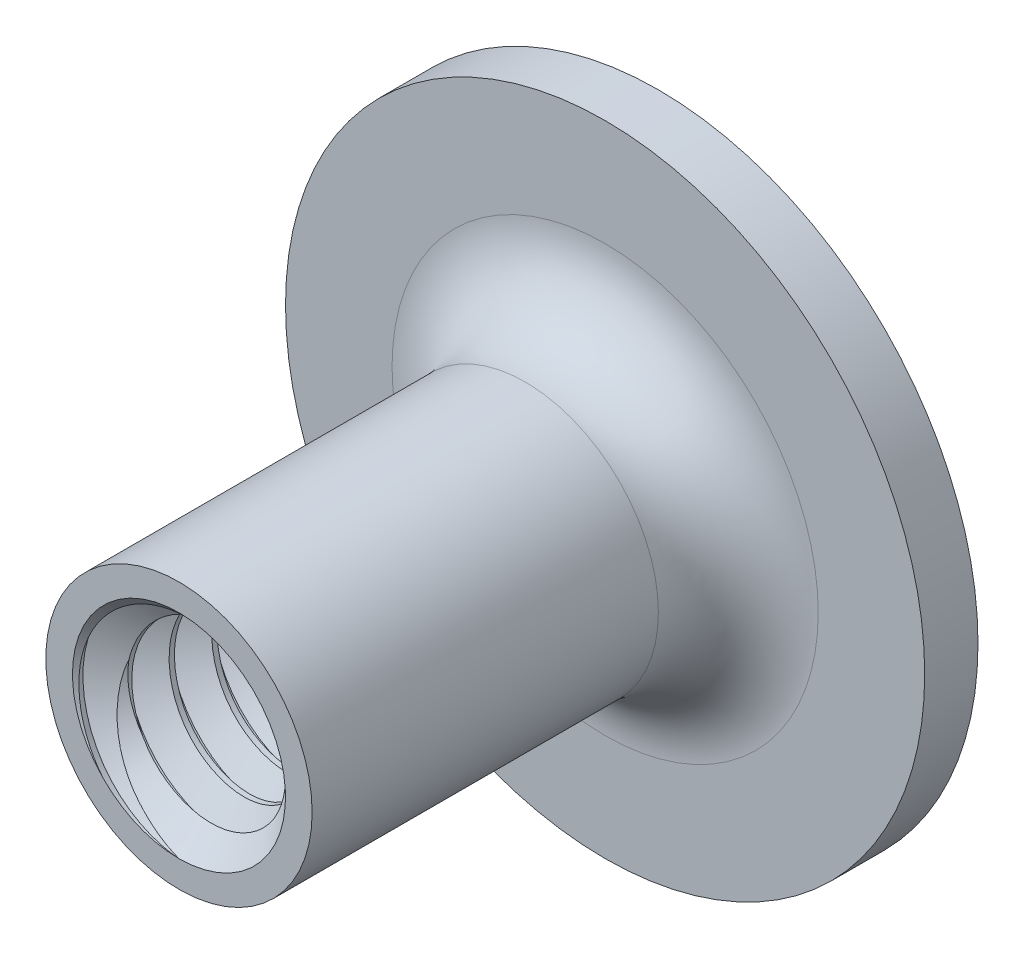
SolidWorks part; units mm, degrees
ref_plane "Front Plane" through (0, 0, 0) normal (0, 0, 1) x (1, 0, 0)
ref_plane "Top Plane" through (0, 0, 0) normal (0, 1, 0) x (1, 0, 0)
ref_plane "Right Plane" through (0, 0, 0) normal (1, 0, 0) x (0, 0, -1)
sketch "Sketch1" plane through (0, 0, 0) normal (0, 0, 1) x (1, 0, 0)
  circle A0 centre (0, 0) radius 9.525
  circle A1 centre (0, 0) radius 3.175
  dimension "D1" = 6.35
  dimension "base dia" = 19.05
extrude "Extrude1" add sketch "Sketch1" along normal blind 1.5875
sketch "Sketch2" plane through (0, 0, 1.5875) normal (0, 0, 1) x (1, 0, 0)
  circle A0 centre (0, 0) radius 3.9688
  circle A1 centre (0, 0) radius 3.175
  dimension "OD" = 6.35
  dimension "Barrel Dia" = 7.9375
extrude "Extrude2" add sketch "Sketch2" along normal blind 12.7
sketch "Sketch3" plane through (0, 0, 0) normal (0, 0, -1) x (-1, 0, 0)
  circle A0 centre (0, 0) radius 3.175 construction
  circle A1 centre (0, 0) radius 3.175
curve "Helix/Spiral1" pitch 1.27 height 15.875 turns 12.5 parameters "pitch"=1.27
sketch "Sketch4" plane through (0, 0, 0) normal (0, 1, 0) x (1, 0, 0)
  line L0 (-3.175, 1.1112) -> (-3.175, 0)
  line L1 (-3.175, 0) -> (-2.3501, 0.4762)
  line L2 (-2.3501, 0.4762) -> (-2.3501, 0.635)
  line L3 (-2.3501, 0.635) -> (-3.175, 1.1112)
  line L4 (-2.3501, 0.5556) -> (-3.175, 0.5556) construction
  line L5 (-2.7626, 0.2381) -> (-2.7626, 0.8731) construction
  dimension "D1" = 0.1588
  dimension "D2" = 0.635
  dimension "D3" = 60
sweep "Sweep1" add profiles "Sketch4" path "Helix/Spiral1"
sketch "Sketch5" plane through (0, 0, 0) normal (0, 0, -1) x (-1, 0, 0)
  circle A1 centre (0, 0) radius 9.525
  circle A2 centre (0, 0) radius 9.525
  dimension "D1" = 0
extrude "Cut-Extrude1" cut sketch "Sketch5" along normal through all
sketch "Sketch6" plane through (0, 0, 0) normal (0, 0, -1) x (-1, 0, 0)
  circle A0 centre (0, 0) radius 3.175 construction
  circle A1 centre (0, 0) radius 3.175
extrude "Cut-Extrude2" cut sketch "Sketch6" against normal through all draft 45
sketch "Sketch7" plane through (0, 0, 14.2875) normal (0, 0, 1) x (1, 0, 0)
  circle A1 centre (0, 0) radius 3.9688
  circle A2 centre (0, 0) radius 3.9688
  dimension "D1" = 0
extrude "Cut-Extrude3" cut sketch "Sketch7" along normal through all
sketch "Sketch8" plane through (0, 0, 14.2875) normal (0, 0, 1) x (1, 0, 0)
  circle A0 centre (0, 0) radius 3.175 construction
  circle A1 centre (0, 0) radius 3.175
extrude "Cut-Extrude4" cut sketch "Sketch8" against normal through all draft 45
fillet "Fillet1" radius 2.3813 1 edges at (3.9688, 0, 1.5875)
equation "\"D1@Sketch1\" = \"OD@Sketch2\""
equation "\"D3@Helix/Spiral1\" = \"height@Extrude2\"+.125"
equation "\"D1@Sketch4\" = \"pitch@Helix/Spiral1\"*.125"
equation "\"D2@Sketch4\" = \"pitch@Helix/Spiral1\"*.5"
equation "\"D1@Fillet1\" = \"base thickness@Extrude1\"*1.50"
